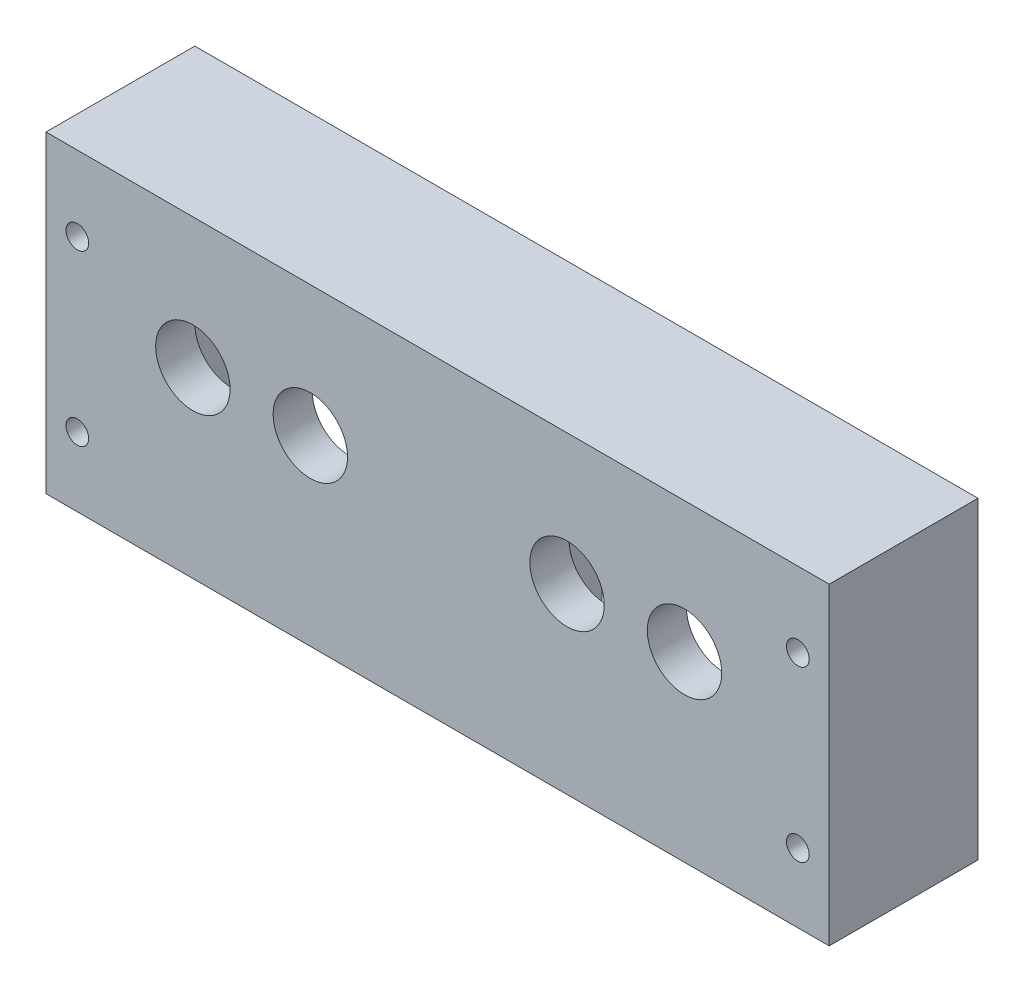
SolidWorks part; units mm, degrees
material "ABS PC"
ref_plane "Front Plane" through (0, 0, 0) normal (0, 0, 1) x (1, 0, 0)
ref_plane "Top Plane" through (0, 0, 0) normal (0, 1, 0) x (1, 0, 0)
ref_plane "Right Plane" through (0, 0, 0) normal (1, 0, 0) x (0, 0, -1)
sketch "Sketch1" plane through (0, 0, 0) normal (0, 0, 1) x (1, 0, 0)
  line L1 (-33.75, 21.5625) -> (66.25, 21.5625)
  line L2 (-33.75, 21.5625) -> (-33.75, -18.4375)
  line L3 (-33.75, -18.4375) -> (66.25, -18.4375)
  line L4 (66.25, 21.5625) -> (66.25, -18.4375)
  dimension "D1" = 100
  dimension "D2" = 40
extrude "Boss-Extrude1" add sketch "Sketch1" along normal blind 38
sketch "Sketch2" plane through (0, 0, 0) normal (0, 0, -1) x (-1, 0, 0)
  line L0 (-66.25, -18.4375) -> (-66.25, 21.5625) construction
  line L1 (-58.25, 18.5625) -> (-18.75, 18.5625)
  line L2 (-58.25, 18.5625) -> (-58.25, -15.4375)
  line L3 (-58.25, -15.4375) -> (-18.75, -15.4375)
  line L4 (-18.75, 18.5625) -> (-18.75, -15.4375)
  line L5 (-13.75, 18.5625) -> (25.75, 18.5625)
  line L6 (-13.75, 18.5625) -> (-13.75, -15.4375)
  line L7 (-13.75, -15.4375) -> (25.75, -15.4375)
  line L8 (25.75, 18.5625) -> (25.75, -15.4375)
  line L9 (33.75, 21.5625) -> (33.75, -18.4375) construction
  line L10 (-66.25, 21.5625) -> (33.75, 21.5625) construction
  line L11 (33.75, -18.4375) -> (-66.25, -18.4375) construction
  dimension "D1" = 8
  dimension "D2" = 8
  dimension "D3" = 5
  dimension "D4" = 3
  dimension "D5" = 3
  dimension "D6" = 3
  dimension "D7" = 3
  dimension "D8" = 39.5
  dimension "D9" = 39.5
extrude "Cut-Extrude2" cut sketch "Sketch2" against normal blind 21 from offset 12 offset against normal yes
sketch "Sketch3" plane through (-3.3623, 0, 0) normal (0, 0, -1) x (-1, 0, 0)
  arc A0 (-55.6418, 7.0775) -> (16.2528, 4.0018) centre (-18.1567, 41.487) ccw construction
  arc A1 (-61.5934, 1.6143) -> (21.716, -1.9497) centre (-18.1567, 41.487) ccw
  arc A2 (-49.6903, 12.5407) -> (10.7896, 9.9533) centre (-18.1567, 41.487) ccw
  arc A3 (-49.6903, 12.5407) -> (-61.5934, 1.6143) centre (-55.6418, 7.0775) ccw
  arc A4 (21.716, -1.9497) -> (10.7896, 9.9533) centre (16.2528, 4.0018) ccw
  point P3 (-20.3315, -9.3502)
extrude "Cut-Extrude3" cut sketch "Sketch3" against normal blind 9 contours A2 A4 A1 A3
sketch "Sketch4" plane through (0, 0, 0) normal (0, 0, -1) x (-1, 0, 0)
  line L0 (-66.25, -18.4375) -> (-66.25, 21.5625) construction
  line L1 (33.75, 21.5625) -> (33.75, -18.4375) construction
  circle A0 centre (-62.25, 11.9848) radius 1.45
  circle A1 centre (-62.25, -9.6166) radius 1.45
  circle A2 centre (29.75, 11.9848) radius 1.45
  circle A3 centre (29.75, -9.6166) radius 1.45
  dimension "D1" = 4
  dimension "D2" = 4
extrude "Cut-Extrude4" cut sketch "Sketch4" against normal up to next
sketch "Sketch5" plane through (0, 21.5625, 0) normal (0, 1, 0) x (1, 0, 0)
  line L0 (-33.75, -38) -> (-33.75, 0) construction
  line L1 (66.25, 0) -> (-33.75, 0)
  line L2 (66.25, 0) -> (66.25, -19)
  line L3 (66.25, -19) -> (-33.75, -19)
  line L4 (-33.75, 0) -> (-33.75, -19)
extrude "Cut-Extrude5" cut sketch "Sketch5" against normal through all
fillet "Fillet1" radius 0.5 8 edges at (18.75, 18.5625, 26) (58.25, 18.5625, 26) (58.25, -15.4375, 26) (18.75, -15.4375, 26) (13.75, -15.4375, 26) (13.75, 18.5625, 26) (-25.75, 18.5625, 26) (-25.75, -15.4375, 26)
sketch "Sketch8" plane through (0, 0, 33) normal (0, 0, -1) x (-1, 0, 0)
  line L8 (-18.25, -14.9375) -> (-18.25, 18.0625)
  line L9 (-19.25, 19.0625) -> (-57.75, 19.0625)
  line L10 (-58.75, 18.0625) -> (-58.75, -14.9375)
  line L11 (-57.75, -15.9375) -> (-19.25, -15.9375)
  line L12 (-18.25, -14.9375) -> (-18.25, 18.0625)
  line L13 (-19.25, 19.0625) -> (-57.75, 19.0625)
  line L14 (-58.75, 18.0625) -> (-58.75, -14.9375)
  line L15 (-57.75, -15.9375) -> (-19.25, -15.9375)
  arc A8 (-18.25, 18.0625) -> (-19.25, 19.0625) centre (-19.25, 18.0625) ccw
  arc A9 (-57.75, 19.0625) -> (-58.75, 18.0625) centre (-57.75, 18.0625) ccw
  arc A10 (-58.75, -14.9375) -> (-57.75, -15.9375) centre (-57.75, -14.9375) ccw
  arc A11 (-19.25, -15.9375) -> (-18.25, -14.9375) centre (-19.25, -14.9375) ccw
  arc A12 (-18.25, 18.0625) -> (-19.25, 19.0625) centre (-19.25, 18.0625) ccw
  arc A13 (-57.75, 19.0625) -> (-58.75, 18.0625) centre (-57.75, 18.0625) ccw
  arc A14 (-58.75, -14.9375) -> (-57.75, -15.9375) centre (-57.75, -14.9375) ccw
  arc A15 (-19.25, -15.9375) -> (-18.25, -14.9375) centre (-19.25, -14.9375) ccw
  dimension "D1" = 0.5
extrude "Cut-Extrude9" cut sketch "Sketch8" along normal blind 0.5 draft 2 from offset 13.5
sketch "Sketch9" plane through (0, 0, 33) normal (0, 0, -1) x (-1, 0, 0)
  line L8 (-14.25, 18.0625) -> (-14.25, -14.9375)
  line L9 (-13.25, -15.9375) -> (25.25, -15.9375)
  line L10 (26.25, -14.9375) -> (26.25, 18.0625)
  line L11 (25.25, 19.0625) -> (-13.25, 19.0625)
  line L12 (-14.25, 18.0625) -> (-14.25, -14.9375)
  line L13 (-13.25, -15.9375) -> (25.25, -15.9375)
  line L14 (26.25, -14.9375) -> (26.25, 18.0625)
  line L15 (25.25, 19.0625) -> (-13.25, 19.0625)
  arc A8 (-14.25, -14.9375) -> (-13.25, -15.9375) centre (-13.25, -14.9375) ccw
  arc A9 (25.25, -15.9375) -> (26.25, -14.9375) centre (25.25, -14.9375) ccw
  arc A10 (26.25, 18.0625) -> (25.25, 19.0625) centre (25.25, 18.0625) ccw
  arc A11 (-13.25, 19.0625) -> (-14.25, 18.0625) centre (-13.25, 18.0625) ccw
  arc A12 (-14.25, -14.9375) -> (-13.25, -15.9375) centre (-13.25, -14.9375) ccw
  arc A13 (25.25, -15.9375) -> (26.25, -14.9375) centre (25.25, -14.9375) ccw
  arc A14 (26.25, 18.0625) -> (25.25, 19.0625) centre (25.25, 18.0625) ccw
  arc A15 (-13.25, 19.0625) -> (-14.25, 18.0625) centre (-13.25, 18.0625) ccw
  dimension "D1" = 0.5
extrude "Cut-Extrude10" cut sketch "Sketch9" along normal blind 0.5 draft 2 from offset 13.5
sketch "Sketch10" plane through (0, 0, 33) normal (0, 0, -1) x (-1, 0, 0)
  circle A0 centre (-47.7772, 4.8517) radius 4.75
  circle A1 centre (-32.7772, 4.8697) radius 4.75
  circle A2 centre (0, 4.8745) radius 4.75
  circle A3 centre (15, 4.8745) radius 4.75
  point P8 (-47.7772, 4.8697)
  dimension "D1" = 15
  dimension "D2" = 15
extrude "Cut-Extrude11" cut sketch "Sketch10" against normal up to next
